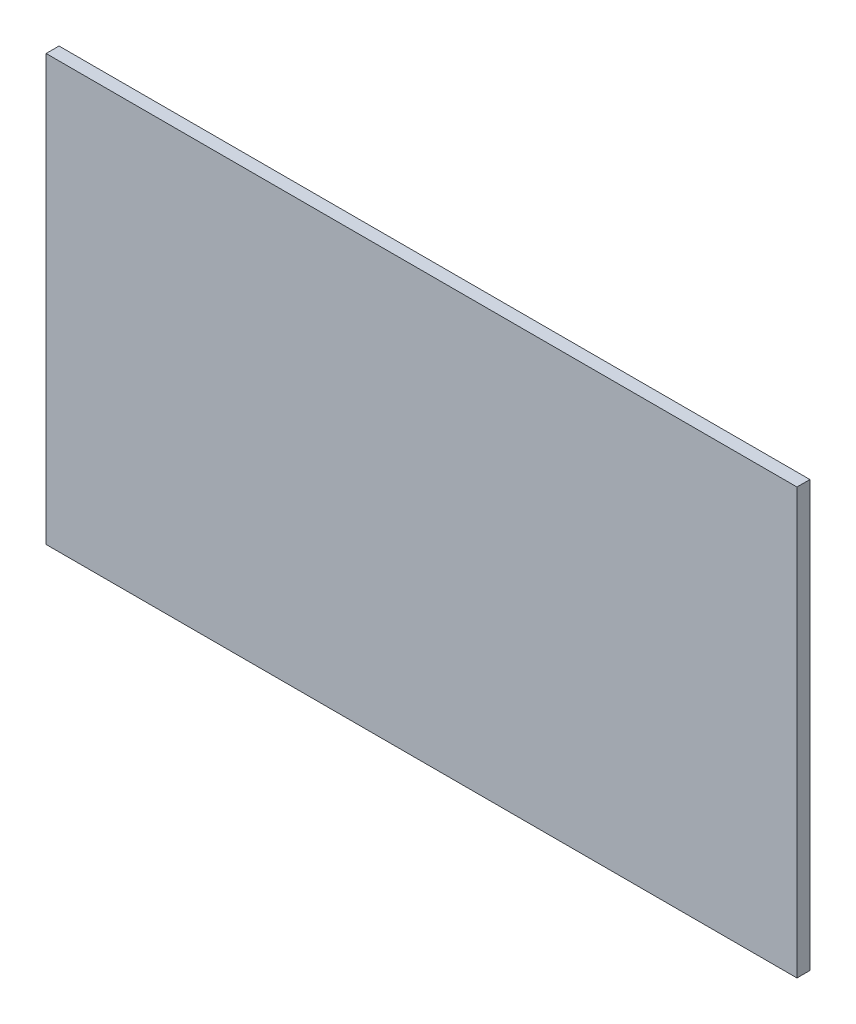
SolidWorks part; units mm, degrees
ref_plane "Plan de face" through (0, 0, 0) normal (0, 0, 1) x (1, 0, 0)
ref_plane "Plan de dessus" through (0, 0, 0) normal (0, 1, 0) x (1, 0, 0)
ref_plane "Plan de droite" through (0, 0, 0) normal (1, 0, 0) x (0, 0, -1)
sketch "Esquisse1" plane through (0, 0, 0) normal (0, 0, 1) x (1, 0, 0)
  line L1 (-189.6573, 78.6929) -> (187.3427, 78.6929)
  line L2 (-189.6573, 78.6929) -> (-189.6573, -134.8071)
  line L3 (-189.6573, -134.8071) -> (187.3427, -134.8071)
  line L4 (187.3427, 78.6929) -> (187.3427, -134.8071)
  dimension "D1" = 377
  dimension "D2" = 213.5
extrude "Boss.-Extru.1" add sketch "Esquisse1" along normal blind 6.5
